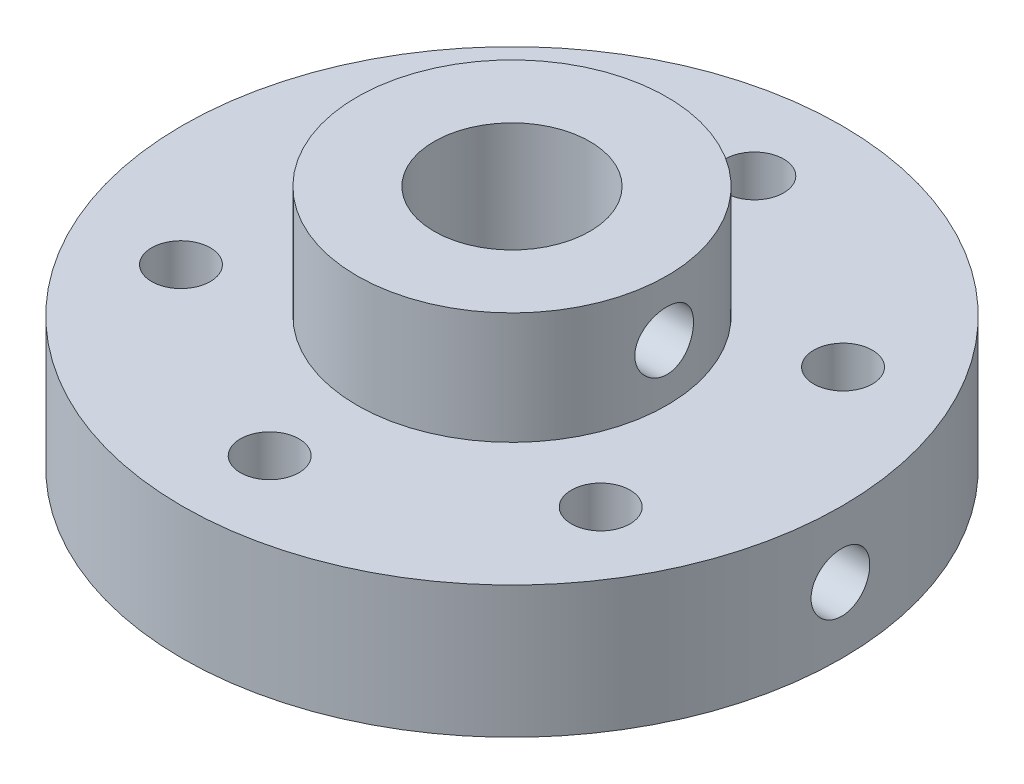
SolidWorks part; units mm, degrees
ref_plane "Front Plane" through (0, 0, 0) normal (0, 0, 1) x (1, 0, 0)
ref_plane "Top Plane" through (0, 0, 0) normal (0, 1, 0) x (1, 0, 0)
ref_plane "Right Plane" through (0, 0, 0) normal (1, 0, 0) x (0, 0, -1)
sketch "Sketch8" plane through (0, 0, 0) normal (0, 1, 0) x (1, 0, 0)
  circle A0 centre (0, 0) radius 12.7
  dimension "D1" = 25.4
extrude "Boss-Extrude6" add sketch "Sketch8" along normal blind 5.08
sketch "Sketch9" plane through (0, 5.08, 0) normal (0, 1, 0) x (1, 0, 0)
  circle A0 centre (0, 0) radius 5.969
  dimension "D1" = 11.938
extrude "Boss-Extrude7" add sketch "Sketch9" along normal blind 4.318
hole_wizard "#4-40 Tapped Hole1" positions "Sketch11" profile "Sketch10" tap size "#4-40" standard "ANSI Inch" end condition through all
sketch "Sketch11" plane through (0, 5.08, 0) normal (0, 1, 0) x (1, 0, 0)
  line L2 (0, 5.969) -> (0, 12.7) construction
  circle A1 centre (0, 0) radius 5.969 construction
  circle A2 centre (0, 0) radius 5.969 construction
  circle A3 centre (0, 0) radius 12.7 construction
  point P0 (0, 9.3345)
sketch "Sketch10" plane through (0, 5.08, -9.3345) normal (1, 0, 0) x (0, 0, 1)
  line L0 (0, 0) -> (0, 5.08)
  line L1 (0, 5.08) -> (1.1303, 5.08)
  line L2 (1.1303, 5.08) -> (1.1303, 0)
  line L5 (1.1303, 0) -> (0, 0)
  line L11 (0, -6.35) -> (0, 107.95) construction
  dimension "Thread Major Dia." = 2.2606
  dimension "Thru Tap Drill Depth" = 5.08
pattern_circular "CirPattern1" count 6 over 360 about axis through (0, 9.398, 0) along (0, -1, 0) of "#4-40 Tapped Hole1"
sketch "Sketch12" plane through (0, 9.398, 0) normal (0, 1, 0) x (1, 0, 0)
  circle A0 centre (0, 0) radius 3
  dimension "D1" = 6
extrude "Cut-Extrude2" cut sketch "Sketch12" against normal through all
hole_wizard "#4-40 Tapped Hole2" positions "Sketch14" profile "Sketch13" tap size "#4-40" standard "ANSI Inch" end condition through all
sketch "Sketch14" plane through (0, 0, 0) normal (1, 0, 0) x (0, 0, -1)
  line L0 (0, 9.398) -> (0, 5.08) construction
  line L1 (5.969, 9.398) -> (-5.969, 9.398) construction
  line L2 (12.7, 5.08) -> (-12.7, 5.08) construction
  line L3 (0, 5.08) -> (0, 0) construction
  point P3 (0, 7.239)
  point P5 (0, 2.54)
sketch "Sketch13" plane through (0, 7.239, 0) normal (0, 1, 0) x (0, 0, 1)
  line L0 (0, 0) -> (0, 12.7)
  line L1 (0, 12.7) -> (1.1303, 12.7)
  line L2 (1.1303, 12.7) -> (1.1303, 0)
  line L5 (1.1303, 0) -> (0, 0)
  line L11 (0, -6.35) -> (0, 107.95) construction
  dimension "Thread Major Dia." = 2.2606
  dimension "Thru Tap Drill Depth" = 12.7
